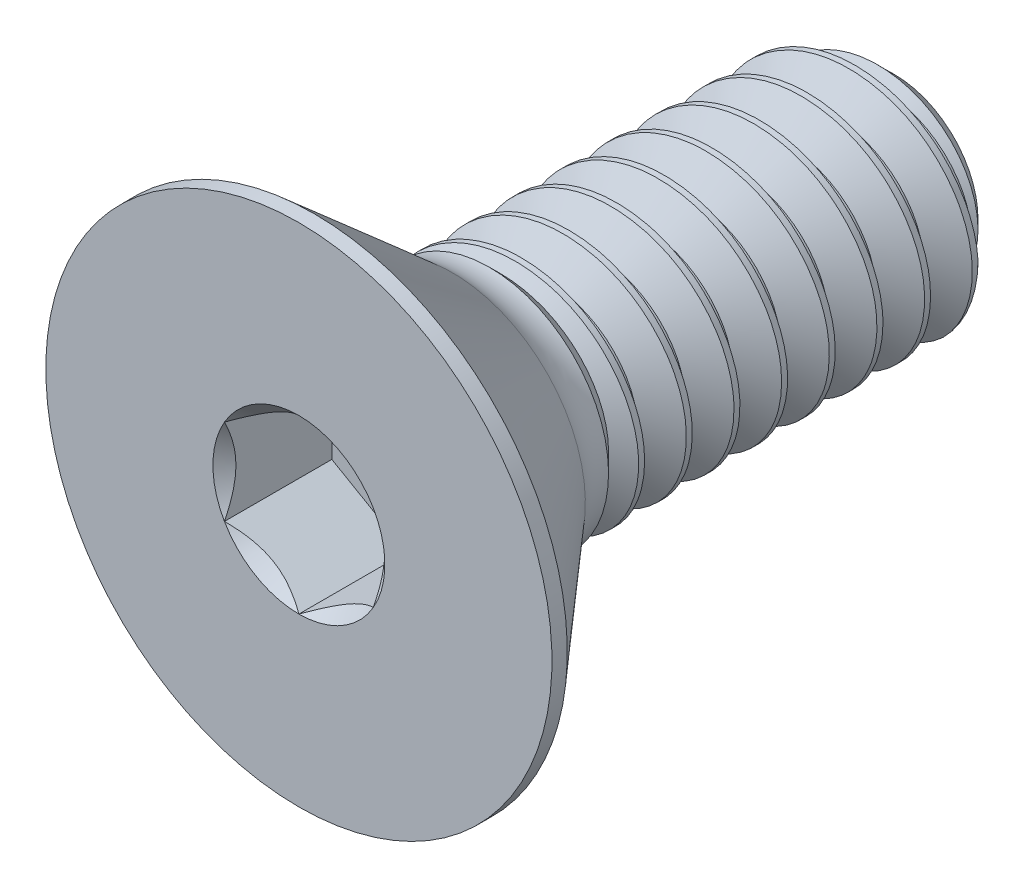
SolidWorks part; units mm, degrees
ref_plane "Front" through (0, 0, 0) normal (0, 0, 1) x (1, 0, 0)
ref_plane "Top" through (0, 0, 0) normal (0, 1, 0) x (1, 0, 0)
ref_plane "Right" through (0, 0, 0) normal (1, 0, 0) x (0, 0, -1)
sketch "Sketch1" plane through (0, 0, 0) normal (1, 0, 0) x (0, 0, -1)
  line L0 (0, 6.7437) -> (0.4089, 6.7437) construction
  line L1 (0.4089, 6.7437) -> (4.0894, 3.5443) construction
  line L2 (0, 3.175) -> (15.875, 3.175)
  line L3 (15.875, 3.175) -> (15.875, 0)
  line L4 (15.875, 0) -> (0, 0)
  line L5 (0, 0) -> (0, 6.7437) construction
  line L6 (0, 6.7437) -> (0, -6.7437) construction
  line L7 (15.875, 3.175) -> (15.875, -3.175) construction
  line L8 (0, -6.7437) -> (0.4089, -6.7437) construction
  line L9 (0.4089, -6.7437) -> (4.0894, -3.5443) construction
  line L11 (0, 3.175) -> (0, 0)
  line L12 (5.0772, 3.175) -> (5.0772, 0) construction
  arc A1 (4.0894, 3.5443) -> (5.0772, 3.175) centre (5.0772, 4.6807) ccw construction
  dimension "D1" = 0.4089
  dimension "Head Ht" = 4.0894
  dimension "Head Dia" = 13.4874
  dimension "Dia" = 6.35
  dimension "Lg" = 15.875
  dimension "Head Angle" = 82
revolve "Revolve1" add sketch "Sketch1" angle 360 about L4
sketch "Sketch3" plane through (0, 0, -15.875) normal (0, 0, -1) x (-1, 0, 0)
  circle A0 centre (0, 0) radius 3.175
curve "Helix/Spiral1" pitch 1.27 height 15.875 radius 3.175 centre (0, 0, -15.875) axis (0, 0, 1) start towards (0, 1, 0)
sketch "Sketch2" plane through (0, 0, 0) normal (1, 0, 0) x (0, 0, -1)
  line L0 (15.875, 3.175) -> (16.9863, 3.175)
  line L1 (16.9863, 3.175) -> (16.51, 2.3501)
  line L2 (16.51, 2.3501) -> (16.3512, 2.3501)
  line L3 (16.3512, 2.3501) -> (15.875, 3.175)
  line L4 (16.1131, 2.7626) -> (16.7481, 2.7626) construction
  dimension "D1" = 60
  dimension "D2" = 0.1588
  dimension "D3" = 0.635
chamfer "Chamfer1" distance 0.9525 angle 45 1 edges at (0, 3.175, -15.875)
sweep "Cut-Sweep1" cut profiles "Sketch2" path "Helix/Spiral1"
sketch "Sketch7" plane through (0, 0, 0) normal (1, 0, 0) x (0, 0, -1)
  line L0 (0, 6.7437) -> (0.4089, 6.7437) construction
  line L1 (0.4089, 6.7437) -> (4.0894, 3.5443) construction
  line L2 (0, 6.7437) -> (0.4089, 6.7437)
  line L3 (0.4089, 6.7437) -> (4.0894, 3.5443)
  line L4 (5.0772, 3.175) -> (5.0772, 0) construction
  line L5 (5.0772, 3.175) -> (5.0772, 0)
  line L7 (0, 0) -> (0, 6.7437) construction
  line L8 (0, 0) -> (0, 6.7437)
  line L9 (0, 0) -> (5.0772, 0)
  line L10 (7.4181, 0) -> (-7.4181, 0) construction
  arc A0 (4.0894, 3.5443) -> (5.0772, 3.175) centre (5.0772, 4.6807) ccw construction
  arc A1 (4.0894, 3.5443) -> (5.0772, 3.175) centre (5.0772, 4.6807) ccw
revolve "Revolve2" add sketch "Sketch7" angle 360 about L9
ref_plane "Plane1" through (0, 0, -5.0772) normal (0, 0, 1) x (1, 0, 0)
sketch "Sketch8" plane through (0, 0, -5.0772) normal (0, 0, 1) x (1, 0, 0)
  circle A0 centre (0, 0) radius 3.175
extrude "Boss-Extrude1" add sketch "Sketch8" against normal through all draft 45
sketch "Sketch11" [suppressed] plane through (0, 0, 0) normal (1, 0, 0) x (0, 0, -1)
  line L0 (4.4996, 0) -> (-4.4996, 0) construction
  line L1 (7.3025, 3.8989) -> (1.7272, 3.8989)
  line L2 (7.3025, 3.8989) -> (7.3025, -3.8989)
  line L3 (7.3025, -3.8989) -> (1.7272, -3.8989)
  line L4 (1.7272, 3.8989) -> (1.7272, -3.8989)
  line L5 (0, 3.8989) -> (0.1727, 3.8989) construction
  line L7 (4.7625, 1.7526) -> (4.7625, 0) construction
  point P4 (1.7272, 0)
  dimension "D1" = 2.54
extrude "Cut-Extrude4" [suppressed] cut sketch "Sketch11" against normal through all and the other way through all
combine bodies "Combine1" operation type add bodies to combine 117 114
sketch "Sketch5" plane through (0, 0, 0) normal (0, 0, 1) x (1, 0, 0)
  line L1 (1.9844, -1.1457) -> (1.9844, 1.1457)
  line L2 (1.9844, 1.1457) -> (0, 2.2914)
  line L3 (0, 2.2914) -> (-1.9844, 1.1457)
  line L4 (-1.9844, 1.1457) -> (-1.9844, -1.1457)
  line L5 (-1.9844, -1.1457) -> (0, -2.2914)
  line L6 (0, -2.2914) -> (1.9844, -1.1457)
  circle A0 centre (0, 0) radius 1.9844 construction
  dimension "Hex" = 3.9688
extrude "Cut-Extrude2" cut sketch "Sketch5" against normal blind 2.8626
sketch "Sketch6" plane through (0, 0, 0) normal (0, 0, 1) x (1, 0, 0)
  circle A0 centre (0, 0) radius 2.2914
extrude "Cut-Extrude3" cut sketch "Sketch6" against normal blind 2.8626 draft 45
sketch "Sketch9" [suppressed] plane through (0, 0, -5.0772) normal (0, 0, 1) x (1, 0, 0)
  circle A1 centre (0, 0) radius 3.175
  circle A2 centre (0, 0) radius 3.175
  point P0 (0, 3.175)
  dimension "D1" = 0
extrude "Boss-Extrude2" [suppressed] add sketch "Sketch9" against normal offset from surface (20.3228 mm away) 44.45 up to face at (0, 2.2225, -15.875)
sketch "Sketch10" plane through (0, 0, 0) normal (1, 0, 0) x (0, 0, -1)
  line L0 (15.875, 3.175) -> (15.875, -3.175) construction
  point P0 (13.97, -3.175)
  dimension "D1" = 1.905
equation "\"D3@Helix/Spiral1\" = \"Lg@Sketch1\""
equation "\"D2@Sketch2\" = \"D4@Helix/Spiral1\" * .125"
equation "\"D3@Sketch2\" = \"D4@Helix/Spiral1\" * .5"
equation "\"D1@Chamfer1\" = \"D4@Helix/Spiral1\" * .75"
equation "\"D1@Cut-Extrude2\" = \"Head Ht@Sketch1\" * .7"
equation "\"D1@Sketch1\" = \"Head Ht@Sketch1\" * .1"
equation "\"D1@Sketch10\" = \"D4@Helix/Spiral1\" * 1.5"
equation "\"D1@Cut-Extrude3\" = \"D1@Cut-Extrude2\""
